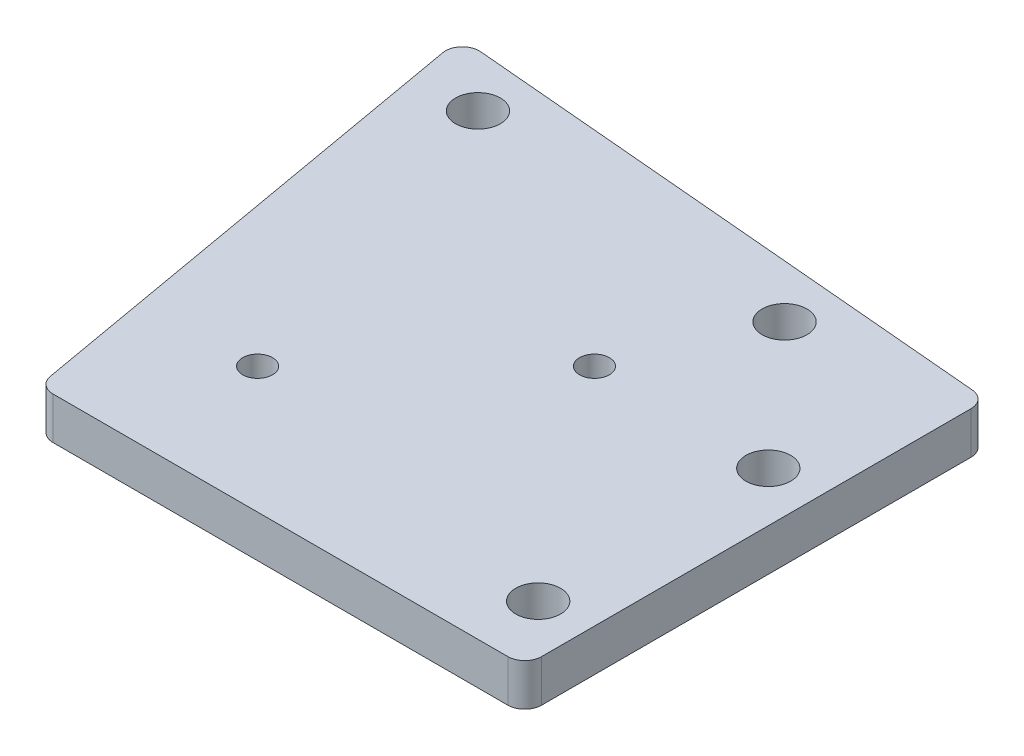
SolidWorks part; units mm, degrees
ref_plane "Front Plane" through (0, 0, 0) normal (0, 0, 1) x (1, 0, 0)
ref_plane "Top Plane" through (0, 0, 0) normal (0, 1, 0) x (1, 0, 0)
ref_plane "Right Plane" through (0, 0, 0) normal (1, 0, 0) x (0, 0, -1)
ref_axis "Axis1" through (0, 55, 0) along (0, -1, 0)
sketch "Sketch1" plane through (0, 0, 0) normal (0, 1, 0) x (1, 0, 0)
  line L0 (46.6348, -101.6681) -> (46.6348, 22.8249) construction
  line L1 (31.6348, -101.6681) -> (31.6348, 24.1373) construction
  line L2 (857.1348, -48.0846) -> (-100.8927, 35.7319) construction
  line L3 (872.1348, -34.3397) -> (-100.2377, 50.7319) construction
  line L4 (46.6348, -31.75) -> (46.6348, 22.8249)
  line L5 (31.6348, -31.75) -> (31.6348, 24.1373) construction
  line L6 (46.6348, 22.8249) -> (-37.5633, 30.1913) construction
  line L7 (46.6348, 37.8822) -> (-40.2599, 45.4845)
  line L8 (46.6348, 22.8249) -> (46.6348, 37.8822)
  line L9 (46.6348, -31.75) -> (-26.6414, -31.75)
  line L10 (-26.6414, -31.75) -> (-40.2599, 45.4845)
  dimension "D1" = 100
  dimension "D2" = 31.75
  dimension "D3" = 31.75
extrude "Boss-Extrude1" add sketch "Sketch1" against normal blind 6.35
hole_wizard "1/4 Clearance Hole1" positions "Sketch9" profile "Sketch10" hole size "1/4" standard "ANSI Inch" end condition through all
sketch "Sketch9" plane through (0, -6.35, 0) normal (0, -1, 0) x (-1, 0, 0)
  line L0 (-39.1348, -31.75) -> (-39.1348, 31.2663) construction
  line L1 (26.6414, -31.75) -> (-46.6348, -31.75) construction
  line L2 (-39.1348, 31.2663) -> (38.9576, 38.0985) construction
  line L3 (40.2599, 45.4845) -> (26.6414, -31.75) construction
  line L5 (-46.6348, 37.8822) -> (40.2599, 45.4845) construction
  line L6 (-46.6348, -31.75) -> (-46.6348, 37.8822) construction
  line L7 (-39.1348, -31.75) -> (-46.6348, -31.75) construction
  line L9 (38.9576, 38.0985) -> (40.2599, 45.4845) construction
  point P26 (-39.1348, -22.225)
  point P28 (-39.1348, 12.4822)
  point P30 (29.4326, 37.2651)
  point P32 (-21.2348, 32.8323)
  dimension "D1" = 7.5
  dimension "D2" = 9.525
  dimension "D3" = 25.4
  dimension "D4" = 25.4
  dimension "D5" = 9.525
sketch "Sketch10" plane through (21.2348, -6.35, -32.8323) normal (1, 0, 0) x (0, 0, -1)
  line L0 (0, 0) -> (0, 6.35)
  line L1 (0, 6.35) -> (3.3782, 6.35)
  line L2 (3.3782, 6.35) -> (3.3782, 0)
  line L5 (3.3782, 0) -> (0, 0)
  line L11 (0, -6.35) -> (0, 107.95) construction
  dimension "Thru Hole Dia." = 6.7564
  dimension "Thru Hole Depth" = 6.35
hole_wizard "#8 Clearance Hole1" positions "Sketch11" profile "Sketch12" hole size "#8" standard "ANSI Inch" end condition through all
sketch "Sketch11" plane through (0, 0, 0) normal (0, 1, 0) x (1, 0, 0)
  circle A0 centre (12.6981, 12.6981) radius 2.159 construction
  circle A1 centre (-12.6981, -12.6981) radius 2.159 construction
  circle A2 centre (12.6981, 12.6981) radius 2.159
  circle A3 centre (-12.6981, -12.6981) radius 2.159
  point P1 (12.6981, 12.6981)
  point P3 (-12.6981, -12.6981)
sketch "Sketch12" plane through (12.6981, 0, -12.6981) normal (1, 0, 0) x (0, 0, 1)
  line L0 (0, 0) -> (0, 6.35)
  line L1 (0, 6.35) -> (2.2479, 6.35)
  line L2 (2.2479, 6.35) -> (2.2479, 0)
  line L5 (2.2479, 0) -> (0, 0)
  line L11 (0, -6.35) -> (0, 107.95) construction
  dimension "Thru Hole Dia." = 4.4958
  dimension "Thru Hole Depth" = 6.35
fillet "Fillet1" radius 2.54 4 edges at (-40.2599, -3.175, -45.4845) (46.6348, -3.175, -37.8822) (-26.6414, -3.175, 31.75) (46.6348, -3.175, 31.75)
